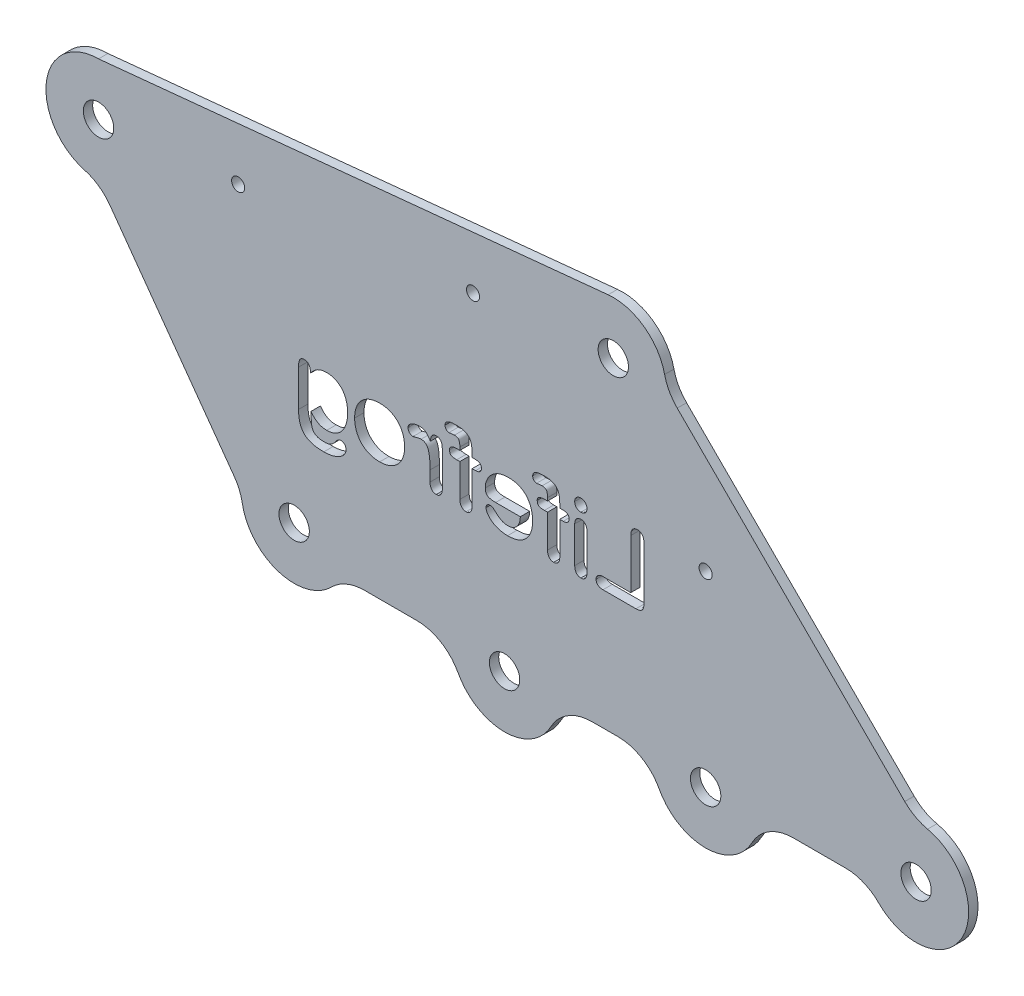
SolidWorks part; units mm, degrees
ref_plane "Front Plane" through (0, 0, 0) normal (0, 0, 1) x (1, 0, 0)
ref_plane "Top Plane" through (0, 0, 0) normal (0, 1, 0) x (1, 0, 0)
ref_plane "Right Plane" through (0, 0, 0) normal (1, 0, 0) x (0, 0, -1)
sketch "Sketch2" plane through (0, 0, 0) normal (0, 0, 1) x (1, 0, 0)
  line L0 (-96.303, -40.0195) -> (103.697, -40.0195) construction
  line L1 (56.1417, 22.4699) -> (-27.5885, 22.4699) construction
  line L2 (56.1417, 22.4699) -> (56.1417, -53.9544) construction
  line L3 (56.1417, -53.9544) -> (-159.2025, -53.9544) construction
  line L4 (-159.2025, 22.4699) -> (-159.2025, -53.9544) construction
  line L5 (-96.303, -40.0195) -> (-53.2713, -40.0195) construction
  line L6 (-96.303, -47.5195) -> (-96.303, -60.0195) construction
  line L7 (-96.303, -60.0195) -> (73.7025, -60.0195) construction
  line L8 (-96.303, -60.0195) -> (-302.9325, -60.0195) construction
  line L9 (-62.0853, -60.0195) -> (-73.2496, -62.9155) construction
  line L10 (-19.0853, -47.5195) -> (-15.8353, -47.5195) construction
  line L11 (25.9147, -47.5195) -> (25.9147, -41.2921) construction
  line L12 (-62.0853, -47.5195) -> (-107.0853, -47.5195) construction
  line L13 (-107.0853, -47.5195) -> (-107.0853, -42.5195) construction
  line L14 (-62.0853, -47.5195) -> (-58.8353, -47.5195) construction
  line L15 (-167.9726, 11.2199) -> (-124.5853, -42.5195) construction
  line L16 (-124.5853, -42.5195) -> (-167.9726, -37.8951) construction
  line L17 (-167.9726, -37.8951) -> (-167.9726, 11.2199) construction
  line L18 (-167.9726, -37.8951) -> (-167.9726, -60.0195) construction
  line L19 (-146.4823, -3.4151) -> (-119.9002, -40.3454)
  line L21 (-148.9187, 22.4699) -> (-39.9417, 33.2746)
  line L24 (-25.1621, 19.6664) -> (23.504, -28.8655)
  line L25 (11.3122, -40.0195) -> (103.697, -40.0195) construction
  line L26 (-41.384, 22.4699) -> (-159.2025, 22.4699) construction
  line L27 (-43.3353, -47.5195) -> (-37.8353, -47.5195)
  line L28 (-0.3353, -47.5195) -> (10.8627, -47.5195)
  line L29 (-80.8353, -47.5195) -> (-92.0333, -47.5195)
  line L30 (-50.8353, -47.5195) -> (-19.0853, -47.5195) construction
  line L31 (-7.8353, -47.5195) -> (25.9147, -47.5195) construction
  line L32 (-148.9187, 11.2199) -> (-38.8318, 22.0795) construction
  arc A0 (-26.3885, 20.8895) -> (-51.3257, 22.4699) centre (-38.8318, 22.0795) ccw construction
  circle A1 centre (-38.8318, 22.0795) radius 3.25 construction
  arc A2 (-74.5853, -47.5195) -> (-51.3689, -53.9544) centre (-62.0853, -47.5195) ccw construction
  circle A3 centre (-62.0853, -47.5195) radius 3.25 construction
  circle A4 centre (25.9147, -42.5195) radius 3.25
  circle A5 centre (-19.0853, -47.5195) radius 3.25 construction
  circle A6 centre (25.9147, -42.5195) radius 17.5 construction
  circle A7 centre (25.9147, -42.5195) radius 3.25 construction
  circle A8 centre (-107.0853, -42.5195) radius 17.5 construction
  circle A9 centre (-107.0853, -42.5195) radius 3.25 construction
  circle A10 centre (-148.9187, 11.2199) radius 19.0539 construction
  circle A11 centre (-148.9187, 11.2199) radius 3.25 construction
  arc A12 (-148.9187, 22.4699) -> (-151.9256, 0.3791) centre (-148.9187, 11.2199) ccw
  arc A13 (-118.1664, -44.4613) -> (-99.1166, -50.4607) centre (-107.0853, -42.5195) ccw
  arc A14 (-27.8565, 24.5507) -> (-39.9417, 33.2746) centre (-38.8318, 22.0795) ccw
  arc A15 (-72.0118, -52.8136) -> (-52.1588, -52.8136) centre (-62.0853, -47.5195) ccw
  arc A16 (-29.0118, -52.8136) -> (-9.1588, -52.8136) centre (-19.0853, -47.5195) ccw
  arc A17 (17.946, -50.4607) -> (28.3768, -31.5422) centre (25.9147, -42.5195) ccw
  arc A18 (-7.6288, -42.5195) -> (-9.0853, -40.0195) centre (-19.0853, -47.5195) ccw construction
  arc A19 (-31.5853, -47.5195) -> (-8.3689, -53.9544) centre (-19.0853, -47.5195) ccw construction
  circle A20 centre (-19.0853, -47.5195) radius 3.25
  circle A21 centre (-62.0853, -47.5195) radius 3.25
  circle A22 centre (-107.0853, -42.5195) radius 3.25
  circle A23 centre (-148.9187, 11.2199) radius 3.25
  circle A24 centre (-38.8318, 22.0795) radius 3.25
  arc A25 (10.8627, -47.5195) -> (17.946, -50.4607) centre (10.8627, -57.5195) cw
  arc A26 (-146.4823, -3.4151) -> (-151.9256, 0.3791) centre (-154.5984, -9.257) ccw
  arc A27 (-119.9002, -40.3454) -> (-118.1664, -44.4613) centre (-128.0164, -46.1873) cw
  arc A28 (-92.0333, -47.5195) -> (-99.1166, -50.4607) centre (-92.0333, -57.5195) ccw
  arc A29 (-80.8353, -47.5195) -> (-72.0118, -52.8136) centre (-80.8353, -57.5195) cw
  arc A30 (-37.8353, -47.5195) -> (-29.0118, -52.8136) centre (-37.8353, -57.5195) cw
  arc A31 (-43.3353, -47.5195) -> (-52.1588, -52.8136) centre (-43.3353, -57.5195) ccw
  arc A33 (-25.1621, 19.6664) -> (-27.8565, 24.5507) centre (-18.1008, 26.7473) cw
  arc A34 (23.504, -28.8655) -> (28.3768, -31.5422) centre (30.5653, -21.7846) ccw
  arc A35 (-0.3353, -47.5195) -> (-9.1588, -52.8136) centre (-0.3353, -57.5195) ccw
  point P67 (15.8369, -47.5195)
  point P70 (-148.9187, -0.0301)
  point P73 (-118.3353, -42.5195)
  point P76 (-97.0075, -47.5195)
  point P79 (-73.3353, -47.5195)
  point P82 (-30.3353, -47.5195)
  point P91 (-27.5818, 22.0795)
  point P94 (25.9147, -31.2695)
  point P98 (0, 0)
  point P99 (0, 0)
  point P100 (0, 0)
  point P101 (-148.9187, 22.4699)
  point P102 (0, 0)
  point P103 (-36.2838, 32.8365)
  dimension "D1" = 25
  dimension "D2" = 6.5
  dimension "D5" = 35
  dimension "D6" = 6.5
  dimension "D10" = 22.5
  dimension "D11" = 22.5
  dimension "D12" = 22.5
  dimension "D13" = 6.5
  dimension "D14" = 6.5
  dimension "D15" = 22.5
  dimension "D16" = 22.5
  dimension "D17" = 22.5
  dimension "D18" = 10
  dimension "D3" = 20
  dimension "D4" = 0
  dimension "D7" = 45
  dimension "D8" = 43
  dimension "D9" = 45
extrude "Boss-Extrude1" add sketch "Sketch2" along normal blind 2
sketch "Sketch5" plane through (0, 0, 2) normal (0, 0, 1) x (1, 0, 0)
  line L1 (-106.4284, -21.9146) -> (-30.7738, -21.9146) construction
  line L2 (-106.4284, -21.9146) -> (-106.4284, -6.1743) construction
  line L3 (-106.4284, -6.1743) -> (-30.7738, -6.1743) construction
  line L4 (-30.7738, -21.9146) -> (-30.7738, -6.1743) construction
sketch "Sketch7" plane through (0, 0, 2) normal (0, 0, 1) x (1, 0, 0)
  line L0 (-148.9187, 11.2199) -> (-38.8318, 22.0795) construction
  line L1 (-148.9187, 11.2199) -> (-107.0853, -42.5195) construction
  line L2 (-107.0853, -42.5195) -> (25.9147, -42.5195) construction
  line L3 (25.9147, -42.5195) -> (-38.8318, 22.0795) construction
  line L5 (-107.0853, -2.5195) -> (-35.0853, -2.5195) construction
  line L6 (25.9147, -42.5195) -> (25.9147, -7.5195) construction
  line L7 (25.9147, -7.5195) -> (-64.0853, -7.5195) construction
  circle A0 centre (-119.0636, 14.1649) radius 1.4
  circle A1 centre (-68.8318, 19.1201) radius 1.4
  circle A5 centre (-19.0853, -7.5195) radius 1.4
  dimension "D1" = 2.8
  dimension "D2" = 2.8
  dimension "D4" = 30
  dimension "D5" = 2.8
  dimension "D6" = 40
  dimension "D3" = 30
  dimension "D7" = 35
  dimension "D9" = 45
extrude "Cut-Extrude4" cut sketch "Sketch7" against normal through all
sketch "Sketch8" plane through (0, 0, 0) normal (0, 0, -1) x (-1, 0, 0)
  text T0 "Lifefrog" font "Arial Rounded MT Bold" height 15
extrude "Cut-Extrude5" cut sketch "Sketch8" against normal through all
sketch "Sketch9" plane through (0, 0, 0) normal (0, 0, -1) x (-1, 0, 0)
  line L0 (59.4615, -14.7017) -> (62.4003, -14.7017) construction
  line L1 (59.4615, -12.7672) -> (62.4003, -12.7672)
  line L2 (59.4615, -16.6363) -> (62.4003, -16.6363)
  arc A0 (59.4615, -12.7672) -> (59.4615, -16.6363) centre (59.4615, -14.7017) ccw
  arc A1 (62.4003, -16.6363) -> (62.4003, -12.7672) centre (62.4003, -14.7017) ccw
  circle A2 centre (88.4097, -16.6363) radius 4.4245
  circle A3 centre (101.377, -16.6363) radius 3.8005
  point P2 (60.9309, -14.7017)
extrude "Cut-Extrude6" cut sketch "Sketch9" against normal blind 10
